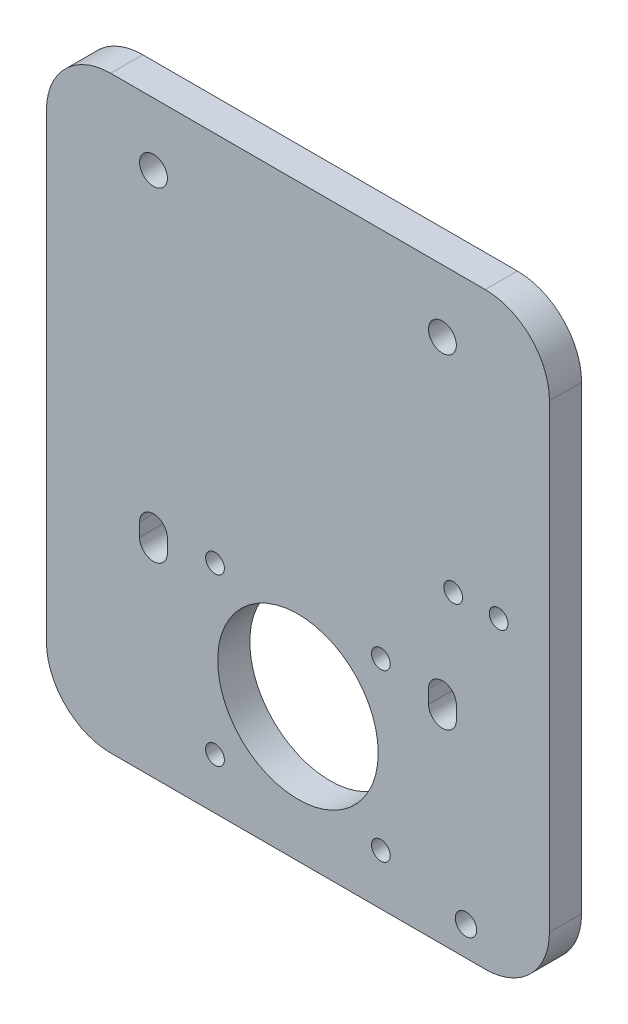
SolidWorks part; units mm, degrees
material "Acrylic (Medium-high impact)"
ref_plane "Спереди" through (0, 0, 0) normal (0, 0, 1) x (1, 0, 0)
ref_plane "Сверху" through (0, 0, 0) normal (0, 1, 0) x (1, 0, 0)
ref_plane "Справа" through (0, 0, 0) normal (1, 0, 0) x (0, 0, -1)
sketch "Model" plane through (0, 0, 0) normal (0, 0, 1) x (1, 0, 0)
  line L4 (-22.7195, 98.3) -> (-31.6357, 98.3) construction
  line L5 (-27, 102.2644) -> (-27, 93.0751) construction
  line L24 (-27, 44.8397) -> (-27, 32.6753) construction
  line L25 (-29.6, 40.1) -> (-29.6, 37.6)
  line L26 (-24.4, 37.6) -> (-24.4, 40.1)
  line L27 (-24.4, 40.1) -> (-24.4, 37.6)
  line L28 (-29.6, 37.6) -> (-29.6, 40.1)
  line L156 (-18.8648, 25) -> (20.0371, 25) construction
  line L157 (13.2088, 9.5) -> (17.9881, 9.5) construction
  line L158 (15.5, 11.4003) -> (15.5, 7.7373) construction
  line L159 (27, 44.8397) -> (27, 32.6753) construction
  line L160 (47, 98) -> (47, 12)
  line L165 (27, 102.2644) -> (27, 93.0751) construction
  line L166 (22.7195, 98.3) -> (31.6357, 98.3) construction
  line L167 (35, 0) -> (-35, 0)
  line L171 (15.5, 38.5997) -> (15.5, 42.2627) construction
  line L172 (13.2088, 40.5) -> (17.9881, 40.5) construction
  line L173 (-13.2088, 40.5) -> (-17.9881, 40.5) construction
  line L174 (-47, 12) -> (-47, 98)
  line L175 (-15.5, 38.5997) -> (-15.5, 42.2627) construction
  line L176 (-15.5, 11.4003) -> (-15.5, 7.7373) construction
  line L177 (-13.2088, 9.5) -> (-17.9881, 9.5) construction
  line L181 (-35, 110) -> (35, 110)
  line L955 (29.6, 37.6) -> (29.6, 40.1)
  line L968 (24.4, 40.1) -> (24.4, 37.6)
  line L1360 (24.4, 37.6) -> (24.4, 40.1)
  line L1373 (29.6, 40.1) -> (29.6, 37.6)
  line L1604 (0, -6.1891) -> (0, 116.9068) construction
  arc A0 (35, 110) -> (47, 98) centre (35, 98) cw
  arc A1 (47, 12) -> (35, 0) centre (35, 12) cw
  arc A2 (-47, 12) -> (-35, 0) centre (-35, 12) ccw
  arc A3 (-47, 98) -> (-35, 110) centre (-35, 98) cw
  circle A4 centre (15.5, 9.5) radius 1.75
  circle A5 centre (15.5, 40.5) radius 1.75
  circle A6 centre (-15.5, 40.5) radius 1.75
  circle A7 centre (-15.5, 9.5) radius 1.75
  circle A8 centre (0, 25) radius 15
  arc A9 (24.4, 40.1) -> (29.6, 40.1) centre (27, 40.1) cw
  arc A10 (24.4, 37.6) -> (29.6, 37.6) centre (27, 37.6) ccw
  circle A19 centre (27, 98.3) radius 2.6
  circle A22 centre (-27, 98.3) radius 2.6
  arc A29 (-24.4, 37.6) -> (-29.6, 37.6) centre (-27, 37.6) cw
  arc A30 (-24.4, 40.1) -> (-29.6, 40.1) centre (-27, 40.1) ccw
  dimension "D1" = 12
  dimension "D11" = 3.5
  dimension "D12" = 30
  dimension "D15" = 2.6
  dimension "D38" = 5.2
  dimension "D2" = 31
  dimension "D3" = 110
  dimension "D4" = 25
  dimension "D5" = 31
  dimension "D6" = 40.1
  dimension "D7" = 94
  dimension "D8" = 54
  dimension "D13" = 5.2
  dimension "D14" = 2.5
  dimension "D36" = 58.2
extrude "Base" add sketch "Model" along normal blind 6 contours A3 L174 A2 L167 A1 L160 A0 L181 A30 L26 A29 L25 A7 A6 A4 A5 A8 A10 L968 A9 L955 region at (0, 57.3106, 0)
sketch "Sketch1" plane through (0, 0, 0) normal (0, 0, -1) x (-1, 0, 0)
  line L1 (-35, 0) -> (35, 0) construction
  line L3 (-47, 98) -> (-47, 12) construction
  circle A0 centre (-29, 58) radius 1.75
  circle A1 centre (-37.5, 58) radius 1.75
  dimension "D1" = 3.5
  dimension "D3" = 9.5
  dimension "D4" = 8.5
  dimension "D5" = 58
extrude "CableChainMount" cut sketch "Sketch1" against normal blind 10
sketch "Sketch2" plane through (0, 0, 6) normal (0, 0, 1) x (1, 0, 0)
  circle A0 centre (31.3948, 5.5057) radius 2
  dimension "D1" = 4
extrude "CableTieMount" cut sketch "Sketch2" against normal through all
